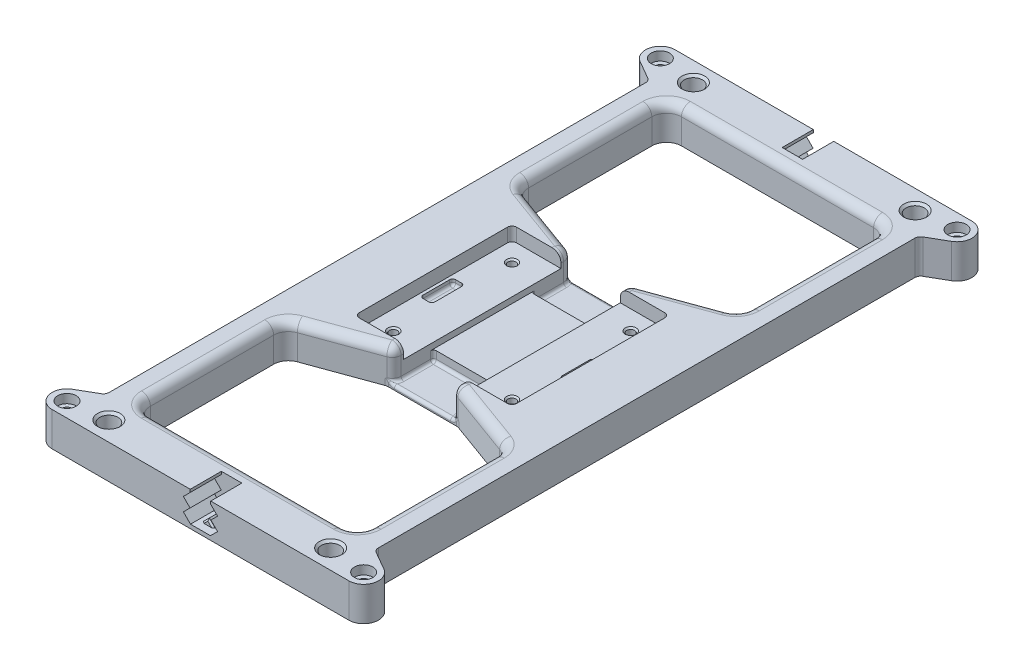
SolidWorks part; units mm, degrees
ref_plane "Front Plane" through (0, 0, 0) normal (0, 0, 1) x (1, 0, 0)
ref_plane "Top Plane" through (0, 0, 0) normal (0, 1, 0) x (1, 0, 0)
ref_plane "Right Plane" through (0, 0, 0) normal (1, 0, 0) x (0, 0, -1)
sketch "Sketch1" plane through (0, 0, 0) normal (0, 1, 0) x (1, 0, 0)
  line L0 (0, 0) -> (0, 90) construction
  line L1 (45.375, 90) -> (-45.375, 90) construction
  line L2 (-45.375, 90) -> (-45.375, 0)
  line L3 (-45.375, 0) -> (45.375, 0)
  line L4 (-45.375, 90) -> (-45.375, 103)
  line L5 (-43.375, 105) -> (43.375, 105)
  line L6 (0, 105) -> (0, 90) construction
  line L7 (45.375, 90) -> (45.375, 103)
  line L8 (45.375, 90) -> (45.375, 0)
  line L14 (-45.375, 93) -> (45.375, 93) construction
  circle A1 centre (-37.375, 98.5) radius 3.075 construction
  circle A2 centre (37.375, 98.5) radius 3.075 construction
  arc A10 (45.375, 103) -> (43.375, 105) centre (43.375, 103) ccw
  arc A11 (-45.375, 103) -> (-43.375, 105) centre (-43.375, 103) cw
  point P42 (45.375, 105)
  point P45 (-45.375, 105)
  dimension "D3" = 6.15
  dimension "D4" = 2
  dimension "D1" = 45.375
  dimension "D2" = 90
  dimension "D6" = 8
  dimension "D7" = 8.5
  dimension "D8" = 12
  dimension "D9" = 3
  dimension "D11" = 105
extrude "Boss-Extrude1" add sketch "Sketch1" along normal blind 11.5
sketch "Sketch3" plane through (0, 11.5, 0) normal (0, 1, 0) x (1, 0, 0)
  line L0 (0, 0) -> (-45.375, 0) construction
  line L2 (0, 0) -> (0, 105) construction
  line L3 (43.375, 105) -> (-43.375, 105) construction
  line L4 (3.96, -16.3) -> (3.96, 16.3)
  line L5 (-2.46, -17.8) -> (2.46, -17.8)
  line L6 (-3.96, 16.3) -> (-3.96, -16.3)
  line L7 (2.46, 17.8) -> (-2.46, 17.8)
  line L8 (0, 17.8) -> (0, -17.8) construction
  arc A0 (-2.46, 17.8) -> (-3.96, 16.3) centre (-2.46, 16.3) ccw
  arc A1 (3.96, 16.3) -> (2.46, 17.8) centre (2.46, 16.3) ccw
  arc A2 (2.46, -17.8) -> (3.96, -16.3) centre (2.46, -16.3) ccw
  arc A3 (-3.96, -16.3) -> (-2.46, -17.8) centre (-2.46, -16.3) ccw
  point P9 (0, 0)
  point P23 (0, 0)
  dimension "D2" = 1.5
  dimension "D1" = 35.6
  dimension "D3" = 7.92
sketch "Sketch4" plane through (0, 11.5, 0) normal (0, 1, 0) x (1, 0, 0)
  circle A2 centre (37.375, 98.5) radius 3.075 construction
  circle A5 centre (-37.375, 98.5) radius 3.075 construction
  circle A10 centre (37.375, 98.5) radius 3.075
  circle A13 centre (-37.375, 98.5) radius 3.075
extrude "Cut-Extrude1" cut sketch "Sketch4" against normal blind 6
sketch "Sketch41" plane through (0, 0, -105) normal (0, 0, -1) x (-1, 0, 0)
  line L0 (5.55, 3.75) -> (3.3, 6) construction
  line L1 (5.55, 3.75) -> (3.3, 1.5) construction
  line L2 (0, 11.5) -> (0, 1.5) construction
  line L3 (0, 1.5) -> (3.3, 1.5) construction
  line L4 (3.3, 6) -> (5.55, 8.25) construction
  line L5 (3.3, 6) -> (3.3, 1.5) construction
  line L6 (5.55, 8.25) -> (3.3, 10.5) construction
  line L7 (3.3, 6) -> (3.3, 10.5) construction
  line L8 (5.55, 3.75) -> (5.55, 8.25) construction
  line L9 (3.3, 10.5) -> (3.3, 11.5) construction
  line L10 (3.3, 1.5) -> (5.55, 1.5) construction
  line L11 (5.55, 1.5) -> (5.55, 3.75) construction
  line L12 (5.55, 3.75) -> (3.3, 3.75) construction
  line L13 (5.55, 8.25) -> (3.3, 8.25) construction
  line L14 (3.3, 6) -> (5.55, 6) construction
  line L15 (-3.3, 11.5) -> (3.3, 11.5)
  line L16 (3.3621, 1.35) -> (-3.3621, 1.35)
  line L17 (0, 1.35) -> (0, 1.5) construction
  line L18 (-3.3, 11.5) -> (-3.45, 11.5)
  line L19 (-3.45, 10.5621) -> (-3.45, 11.5)
  line L20 (3.45, 10.5621) -> (3.45, 11.5)
  line L21 (5.7621, 8.25) -> (3.45, 10.5621)
  line L22 (3.5121, 6) -> (5.7621, 8.25)
  line L23 (5.7621, 3.75) -> (3.5121, 6)
  line L24 (5.7621, 3.75) -> (3.3621, 1.35)
  line L25 (3.3, 11.5) -> (3.45, 11.5)
  line L26 (-5.7621, 8.25) -> (-3.45, 10.5621)
  line L27 (-3.5121, 6) -> (-5.7621, 8.25)
  line L28 (-5.7621, 3.75) -> (-3.5121, 6)
  line L29 (-5.7621, 3.75) -> (-3.3621, 1.35)
  line L30 (-43.375, 11.5) -> (43.375, 11.5) construction
  dimension "D1" = 1
  dimension "D2" = 45
  dimension "D3" = 45
  dimension "D4" = 45
  dimension "D5" = 45
  dimension "D6" = 3.3
  dimension "D7" = 10
  dimension "D8" = 0.15
  dimension "D9" = 0.15
  dimension "D10" = 0.15
  dimension "D11" = 0.15
  dimension "D12" = 0.15
  dimension "D13" = 0.15
extrude "Cut-Extrude31" cut sketch "Sketch41" against normal blind 10.5
sketch "Sketch42" plane through (0, 0, -94.5) normal (0, 0, -1) x (-1, 0, 0)
  line L0 (0, 1.35) -> (0, 3.35) construction
  line L1 (-3.3621, 1.35) -> (3.3621, 1.35) construction
  line L2 (0, 3.35) -> (2, 1.35)
  line L3 (2, 1.35) -> (-2, 1.35)
  line L4 (0, 3.35) -> (-2, 1.35)
  dimension "D1" = 45
  dimension "D2" = 2
extrude "Boss-Extrude9" add sketch "Sketch42" along normal blind 8
chamfer "Chamfer7" distance 0.5 angle 45 2 edges at (1, 2.35, -102.5) (-1, 2.35, -102.5)
mirror "Mirror1" about plane through (-45.375, 11.5, 0) normal (0, 0, -1) of "Boss-Extrude1", "Cut-Extrude1", "Cut-Extrude31", "Boss-Extrude9", "Chamfer7"
sketch "Sketch28" plane through (0, 11.5, 0) normal (0, 1, 0) x (1, 0, 0)
  line L1 (-26, 26) -> (26, 26) construction
  line L2 (-26, 26) -> (-26, -26) construction
  line L3 (-26, -26) -> (26, -26) construction
  line L4 (26, 26) -> (26, -26) construction
  line L5 (-26, 26) -> (26, -26) construction
  line L6 (-26, -26) -> (26, 26) construction
  line L7 (-25, 26.5) -> (25, 26.5)
  line L8 (-26.5, 25) -> (-26.5, -25)
  line L9 (-25, -26.5) -> (25, -26.5)
  line L10 (26.5, 25) -> (26.5, -25)
  line L11 (-26.5, 26.5) -> (26.5, -26.5) construction
  line L12 (-26.5, -26.5) -> (26.5, 26.5) construction
  arc A0 (-25, -26.5) -> (-26.5, -25) centre (-25, -25) cw
  arc A1 (25, -26.5) -> (26.5, -25) centre (25, -25) ccw
  arc A2 (25, 26.5) -> (26.5, 25) centre (25, 25) cw
  arc A3 (-25, 26.5) -> (-26.5, 25) centre (-25, 25) ccw
  point P0 (0, 0)
  point P6 (0, 0)
  dimension "D4" = 1.5
  dimension "D1" = 52
  dimension "D2" = 0.5
  dimension "D3" = 0.5
extrude "Cut-Extrude21" cut sketch "Sketch28" against normal blind 4.6
sketch "Sketch36" plane through (0, 6.9, 0) normal (0, 1, 0) x (1, 0, 0)
  line L2 (-26, 26) -> (-26, -26) construction
  line L3 (-26, 26) -> (26, 26) construction
  circle A0 centre (-20, 20) radius 1.35
  circle A1 centre (20, 20) radius 1.35
  circle A2 centre (20, -20) radius 1.35
  circle A3 centre (-20, -20) radius 1.35
  point P15 (0, 0)
  dimension "D3" = 2.7
  dimension "D1" = 6
  dimension "D2" = 6
  dimension "D4" = 4
extrude "Cut-Extrude28" cut sketch "Sketch36" against normal blind 5
chamfer "Chamfer6" distance 0.5 angle 45 4 edges at (-20, 6.9, 21.35) (20, 6.9, 21.35) (20, 6.9, -18.65) (-20, 6.9, -18.65)
sketch "Sketch29" plane through (0, 6.9, 0) normal (0, 1, 0) x (1, 0, 0)
  line L0 (0, 0) -> (26.5, 0) construction
  line L5 (0, 0) -> (0, -26.5) construction
  line L6 (-25, -26.5) -> (25, -26.5) construction
  line L7 (26.5, -25) -> (26.5, 25) construction
  line L8 (-10, 26.5) -> (10, 16.5) construction
  line L9 (-10, 16.5) -> (10, 26.5) construction
  line L10 (-10, -16.5) -> (10, -16.5)
  line L11 (-10, -16.5) -> (-10, -26.5)
  line L12 (-10, -26.5) -> (10, -26.5)
  line L13 (10, -16.5) -> (10, -26.5)
  line L14 (-10, -16.5) -> (10, -26.5) construction
  line L15 (-10, -26.5) -> (10, -16.5) construction
  line L16 (10, 16.5) -> (10, 26.5)
  line L17 (-10, 26.5) -> (10, 26.5)
  line L18 (-10, 16.5) -> (-10, 26.5)
  line L19 (-10, 16.5) -> (10, 16.5)
  point P4 (0, -21.5)
  point P17 (0, 21.5)
  dimension "D1" = 20
  dimension "D2" = 10
extrude "Cut-Extrude22" cut sketch "Sketch29" against normal blind 5.5
sketch "Sketch25" plane through (0, 0, 0) normal (0, -1, 0) x (1, 0, 0)
  line L0 (0, 0) -> (45.375, 0) construction
  line L1 (45.375, 103) -> (45.375, -103) construction
  line L2 (0, 0) -> (0, 105) construction
  line L4 (52.5, 95.6699) -> (46.375, 92.1336)
  line L5 (50, 100) -> (45.375, 100) construction
  line L6 (45.375, 90.4016) -> (45.375, 103)
  line L8 (43.375, 105) -> (50, 105)
  line L9 (-50, 100) -> (-45.375, 100) construction
  line L10 (-43.375, 105) -> (-50, 105)
  line L11 (-45.375, 90.4016) -> (-45.375, 103)
  line L12 (-52.5, 95.6699) -> (-46.375, 92.1336)
  line L13 (-50, -100) -> (-45.375, -100) construction
  line L14 (50, -100) -> (45.375, -100) construction
  line L15 (-52.5, -95.6699) -> (-46.375, -92.1336)
  line L16 (-45.375, -90.4016) -> (-45.375, -103)
  line L17 (-43.375, -105) -> (-50, -105)
  line L18 (43.375, -105) -> (50, -105)
  line L19 (45.375, -90.4016) -> (45.375, -103)
  line L20 (52.5, -95.6699) -> (46.375, -92.1336)
  line L21 (43.375, 105) -> (-43.375, 105) construction
  circle A0 centre (50, 100) radius 1.7
  arc A1 (52.5, 95.6699) -> (50, 105) centre (50, 100) ccw
  arc A2 (46.375, 92.1336) -> (45.375, 90.4016) centre (47.375, 90.4016) ccw
  arc A17 (45.375, 103) -> (43.375, 105) centre (43.375, 103) ccw
  arc A18 (-45.375, 103) -> (-43.375, 105) centre (-43.375, 103) cw
  arc A19 (-46.375, 92.1336) -> (-45.375, 90.4016) centre (-47.375, 90.4016) cw
  arc A20 (-52.5, 95.6699) -> (-50, 105) centre (-50, 100) cw
  circle A21 centre (-50, 100) radius 1.7
  circle A22 centre (-50, -100) radius 1.7
  arc A23 (-52.5, -95.6699) -> (-50, -105) centre (-50, -100) ccw
  arc A24 (-46.375, -92.1336) -> (-45.375, -90.4016) centre (-47.375, -90.4016) ccw
  arc A25 (-45.375, -103) -> (-43.375, -105) centre (-43.375, -103) ccw
  arc A26 (45.375, -103) -> (43.375, -105) centre (43.375, -103) cw
  arc A27 (46.375, -92.1336) -> (45.375, -90.4016) centre (47.375, -90.4016) cw
  arc A28 (52.5, -95.6699) -> (50, -105) centre (50, -100) cw
  circle A29 centre (50, -100) radius 1.7
  arc A30 (45.375, 103) -> (43.375, 105) centre (43.375, 103) ccw construction
  dimension "D1" = 3.4
  dimension "D2" = 10
  dimension "D6" = 2
  dimension "D3" = 4.625
  dimension "D5" = 60
extrude "Boss-Extrude7" add sketch "Sketch25" against normal up to surface (11.5 mm away) up to face at (0, 11.5, 0)
sketch "Sketch27" plane through (0, 11.5, 0) normal (0, 1, 0) x (1, 0, 0)
  circle A4 centre (-50, -100) radius 3.1
  circle A5 centre (50, -100) radius 3.1
  circle A6 centre (-50, 100) radius 3.1
  circle A7 centre (50, 100) radius 3.1
  dimension "D1" = 6.2
extrude "Cut-Extrude20" cut sketch "Sketch27" against normal blind 3
sketch "Sketch37" plane through (0, 6.9, 0) normal (0, 1, 0) x (1, 0, 0)
  line L0 (45.375, 0) -> (0, 0) construction
  line L1 (45.375, -90.4016) -> (45.375, 90.4016) construction
  line L2 (0, 0) -> (-45.375, 0) construction
  line L3 (26.5, -25) -> (26.5, 25) construction
  line L4 (24.5, 5.5) -> (22.5, 5.5)
  line L5 (25.5, 4.5) -> (25.5, -4.5)
  line L6 (24.5, -5.5) -> (22.5, -5.5)
  line L7 (21.5, 4.5) -> (21.5, -4.5)
  line L8 (25.5, 5.5) -> (21.5, -5.5) construction
  line L9 (25.5, -5.5) -> (21.5, 5.5) construction
  line L10 (0, 0) -> (0, 26.5) construction
  line L11 (-10, 16.5) -> (10, 16.5) construction
  line L12 (-24.5, -5.5) -> (-22.5, -5.5)
  line L13 (-25.5, 4.5) -> (-25.5, -4.5)
  line L14 (-24.5, 5.5) -> (-22.5, 5.5)
  line L15 (-21.5, 4.5) -> (-21.5, -4.5)
  line L21 (10, 16.5) -> (10, -16.5)
  line L23 (25, 26.5) -> (-25, 26.5) construction
  line L24 (-10, 16.5) -> (10, 16.5)
  line L25 (-10, 16.5) -> (-10, -16.5)
  line L26 (-10, -16.5) -> (10, -16.5)
  arc A0 (22.5, -5.5) -> (21.5, -4.5) centre (22.5, -4.5) cw
  arc A1 (25.5, -4.5) -> (24.5, -5.5) centre (24.5, -4.5) cw
  arc A2 (22.5, 5.5) -> (21.5, 4.5) centre (22.5, 4.5) ccw
  arc A3 (24.5, 5.5) -> (25.5, 4.5) centre (24.5, 4.5) cw
  arc A4 (-22.5, 5.5) -> (-21.5, 4.5) centre (-22.5, 4.5) cw
  arc A5 (-24.5, 5.5) -> (-25.5, 4.5) centre (-24.5, 4.5) ccw
  arc A6 (-22.5, -5.5) -> (-21.5, -4.5) centre (-22.5, -4.5) ccw
  arc A7 (-25.5, -4.5) -> (-24.5, -5.5) centre (-24.5, -4.5) ccw
  point P5 (23.5, 0)
  point P54 (10, 0)
  point P56 (-10, 0)
  dimension "D4" = 1
  dimension "D1" = 11
  dimension "D2" = 4
  dimension "D3" = 3
extrude "Cut-Extrude29" cut sketch "Sketch37" against normal blind 2
fillet "Fillet20" radius 1 16 edges at (25.2071, 4.9, -5.2071) (25.5, 4.9, 0) (25.2071, 4.9, 5.2071) (23.5, 4.9, 5.5) (21.7929, 4.9, 5.2071) (21.5, 4.9, 0) (21.7929, 4.9, -5.2071) (-21.7929, 4.9, -5.2071) (-21.5, 4.9, 0) (-21.7929, 4.9, 5.2071) (-23.5, 4.9, 5.5) (-25.2071, 4.9, 5.2071) (-25.5, 4.9, 0) (-25.2071, 4.9, -5.2071) (23.5, 4.9, -5.5) (-23.5, 4.9, -5.5)
sketch "Sketch38" plane through (0, 11.5, 0) normal (0, 1, 0) x (1, 0, 0)
  line L0 (11.9739, -30.2185) -> (34.0851, -38.2663)
  line L1 (37.375, -42.9647) -> (37.375, -84.5)
  line L2 (32.375, -89.5) -> (-32.375, -89.5)
  line L3 (0, -89.5) -> (0, -26.5) construction
  line L4 (-10, -26.5) -> (10, -26.5) construction
  line L6 (45.375, -90.4016) -> (45.375, 90.4016) construction
  line L7 (-3.45, -94.5) -> (3.45, -94.5) construction
  line L9 (-25, -26.5) -> (25, -26.5) construction
  line L12 (0, 0) -> (45.375, 0) construction
  line L13 (0, 89.5) -> (0, 26.5) construction
  line L20 (10, -27.3994) -> (10, -26.5)
  line L21 (10, -26.5) -> (25, -26.5) construction
  line L22 (10, -26.5) -> (-10, -26.5)
  line L23 (10, -26.5) -> (10, 26.5) construction
  line L24 (-10, -27.3994) -> (-10, -26.5)
  line L25 (-37.375, -42.9647) -> (-37.375, -84.5)
  line L26 (-11.9739, -30.2185) -> (-34.0851, -38.2663)
  line L27 (-11.9739, 30.2185) -> (-34.0851, 38.2663)
  line L28 (-37.375, 42.9647) -> (-37.375, 84.5)
  line L29 (-10, 27.3994) -> (-10, 26.5)
  line L30 (10, 26.5) -> (-10, 26.5)
  line L31 (10, 27.3994) -> (10, 26.5)
  line L32 (32.375, 89.5) -> (-32.375, 89.5)
  line L33 (37.375, 42.9647) -> (37.375, 84.5)
  line L34 (11.9739, 30.2185) -> (34.0851, 38.2663)
  arc A0 (37.375, -42.9647) -> (34.0851, -38.2663) centre (32.375, -42.9647) ccw
  arc A1 (37.375, -84.5) -> (32.375, -89.5) centre (32.375, -84.5) cw
  arc A8 (11.9739, -30.2185) -> (10, -27.3994) centre (13, -27.3994) cw
  arc A9 (-11.9739, -30.2185) -> (-10, -27.3994) centre (-13, -27.3994) ccw
  arc A10 (-37.375, -84.5) -> (-32.375, -89.5) centre (-32.375, -84.5) ccw
  arc A11 (-37.375, -42.9647) -> (-34.0851, -38.2663) centre (-32.375, -42.9647) cw
  arc A12 (-37.375, 42.9647) -> (-34.0851, 38.2663) centre (-32.375, 42.9647) ccw
  arc A13 (-37.375, 84.5) -> (-32.375, 89.5) centre (-32.375, 84.5) cw
  arc A14 (-11.9739, 30.2185) -> (-10, 27.3994) centre (-13, 27.3994) cw
  arc A15 (11.9739, 30.2185) -> (10, 27.3994) centre (13, 27.3994) ccw
  arc A16 (37.375, 84.5) -> (32.375, 89.5) centre (32.375, 84.5) ccw
  arc A17 (37.375, 42.9647) -> (34.0851, 38.2663) centre (32.375, 42.9647) cw
  point P49 (10, -29.5)
  point P60 (-10, -29.5)
  point P67 (-10, 29.5)
  point P68 (10, 29.5)
  dimension "D4" = 5
  dimension "D6" = 3
  dimension "D1" = 5
  dimension "D2" = 8
  dimension "D3" = 20
  dimension "D5" = 3
extrude "Cut-Extrude30" cut sketch "Sketch38" against normal through all
sketch "Sketch39" plane through (0, 0, 0) normal (0, -1, 0) x (1, 0, 0)
  line L0 (0, 0) -> (45.375, 0) construction
  line L1 (45.375, 90.4016) -> (45.375, -90.4016) construction
  line L2 (-11.9739, 30.2185) -> (11.9739, 30.2185)
  line L3 (10, 27.3994) -> (10, 26.5) construction
  line L4 (10, 26.5) -> (-10, 26.5) construction
  line L5 (-10, 26.5) -> (-10, 27.3994) construction
  line L6 (10, 27.3994) -> (10, 26.5)
  line L7 (10, 26.5) -> (-10, 26.5)
  line L8 (-10, 26.5) -> (-10, 27.3994)
  line L9 (-10, -26.5) -> (-10, -27.3994)
  line L10 (10, -26.5) -> (-10, -26.5)
  line L11 (10, -27.3994) -> (10, -26.5)
  line L12 (-11.9739, -30.2185) -> (11.9739, -30.2185)
  arc A0 (11.9739, 30.2185) -> (10, 27.3994) centre (13, 27.3994) ccw construction
  arc A1 (-10, 27.3994) -> (-11.9739, 30.2185) centre (-13, 27.3994) ccw construction
  arc A2 (11.9739, 30.2185) -> (10, 27.3994) centre (13, 27.3994) ccw
  arc A3 (-10, 27.3994) -> (-11.9739, 30.2185) centre (-13, 27.3994) ccw
  arc A4 (-10, -27.3994) -> (-11.9739, -30.2185) centre (-13, -27.3994) cw
  arc A5 (11.9739, -30.2185) -> (10, -27.3994) centre (13, -27.3994) cw
extrude "Boss-Extrude8" add sketch "Sketch39" against normal up to surface (1.4 mm away) up to face at (0, 1.4, 21.5)
fillet "Fillet21" radius 1 14 edges at (0, 1.4, -16.5) (0, 1.4, 16.5) (-10.5425, 1.4, -29.1201) (10.5425, 1.4, -29.1201) (-10.5425, 1.4, 29.1201) (10.5425, 1.4, 29.1201) (-10, 1.4, -21.9497) (-10, 3.15, -16.5) (10, 1.4, -21.9497) (10, 3.15, -16.5) (-10, 3.15, 16.5) (-10, 1.4, 21.9497) (10, 3.15, 16.5) (10, 1.4, 21.9497)
fillet "Fillet22" radius 3 26 edges at (10, 11.5, -26.9497) (10.5425, 11.5, -29.1201) (23.0295, 11.5, -34.2424) (36.4708, 11.5, -40.0968) (37.375, 11.5, -63.7324) (35.9105, 11.5, -88.0355) (0, 11.5, -89.5) (-35.9105, 11.5, -88.0355) (-37.375, 11.5, -63.7324) (-36.4708, 11.5, -40.0968) (-10, 11.5, -26.9497) (-10.5425, 11.5, -29.1201) (-10, 11.5, 26.9497) (-10.5425, 11.5, 29.1201) (10, 11.5, 26.9497) (10.5425, 11.5, 29.1201) (23.0295, 11.5, 34.2424) (36.4708, 11.5, 40.0968) (37.375, 11.5, 63.7324) (35.9105, 11.5, 88.0355) (0, 11.5, 89.5) (-35.9105, 11.5, 88.0355) (-37.375, 11.5, 63.7324) (-36.4708, 11.5, 40.0968) (-23.0295, 11.5, -34.2424) (-23.0295, 11.5, 34.2424)
fillet "Fillet24" radius 3 4 edges at (-11.9739, 1.2, 30.2185) (11.9739, 1.2, 30.2185) (11.9739, 1.2, -30.2185) (-11.9739, 1.2, -30.2185)
fillet "Fillet25" radius 1 10 edges at (0, 1.4, 30.2185) (0, 1.4, -30.2185) (-12.1079, 2.1665, -30.2926) (-10.8141, 1.4985, -30.2185) (12.1976, 2.1847, -30.3144) (10.9036, 1.5265, -30.2185) (12.1079, 2.1665, 30.2926) (10.8141, 1.4985, 30.2185) (-12.1976, 2.1847, 30.3144) (-10.9036, 1.5265, 30.2185)
chamfer "Chamfer8" distance 0.75 angle 45 4 edges at (37.375, 11.5, -95.425) (-37.375, 11.5, -95.425) (-37.375, 11.5, 95.425) (37.375, 11.5, 95.425)
equation "\"D3@Sketch28\"=\"D2@Sketch28\""
equation "\"D2@Sketch36\"=\"D1@Sketch36\""
